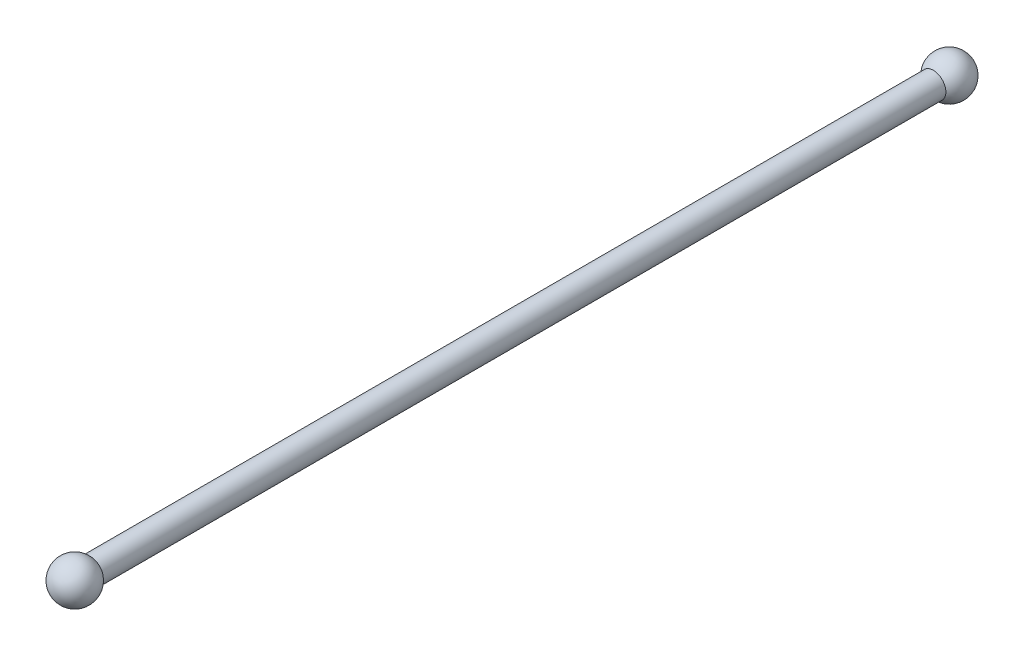
SolidWorks part; units mm, degrees
ref_plane "Front Plane" through (0, 0, 0) normal (0, 0, 1) x (1, 0, 0)
ref_plane "Top Plane" through (0, 0, 0) normal (0, 1, 0) x (1, 0, 0)
ref_plane "Right Plane" through (0, 0, 0) normal (1, 0, 0) x (0, 0, -1)
sketch "Sketch1" plane through (0, 0, 0) normal (0, 0, 1) x (1, 0, 0)
  circle A0 centre (0, 0) radius 1.73
  dimension "D1" = 3.46
extrude "Boss-Extrude1" add sketch "Sketch1" along normal blind 116
dome "Dome1" faces to dome 1 distance 5 reverse direction no elliptical dome no face at (1.73, 0, 0) parameters "D1"=5
dome "Dome2" faces to dome 1 distance 5 reverse direction no elliptical dome no face at (1.73, 0, 116) parameters "D1"=5
